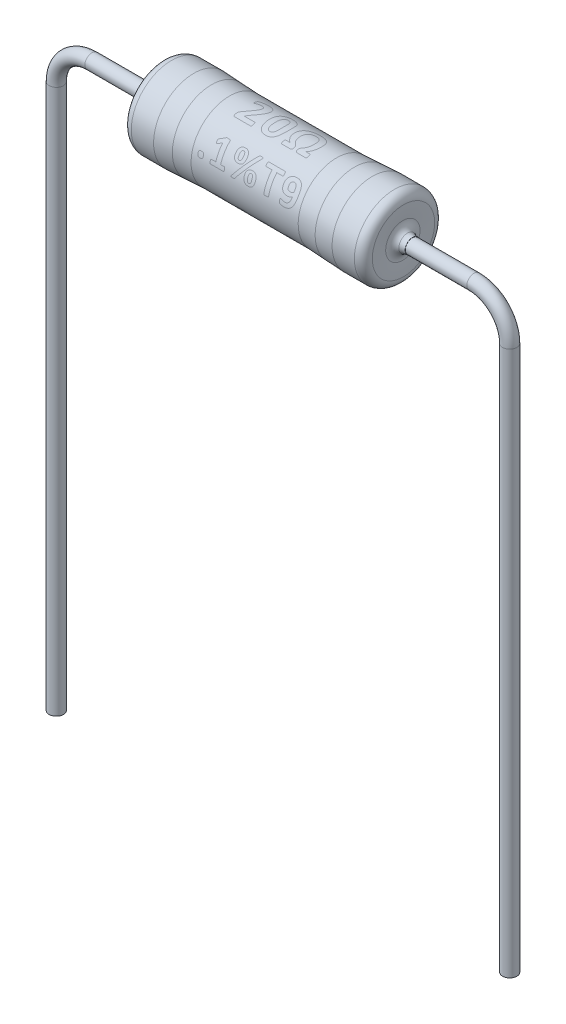
SolidWorks part; units mm, degrees
other "WIRE"
other "RESISTOR"
ref_plane "Front Plane" through (0, 0, 0) normal (0, 0, 1) x (1, 0, 0)
ref_plane "Top Plane" through (0, 0, 0) normal (0, 1, 0) x (1, 0, 0)
ref_plane "Right Plane" through (0, 0, 0) normal (1, 0, 0) x (0, 0, -1)
sketch "Sketch Wire Length" plane through (0, 0, 0) normal (0, 0, 1) x (1, 0, 0)
  line L0 (-10.7, 0) -> (10.7, 0)
  line L1 (12.7, -2) -> (12.7, -32.5084)
  line L2 (-12.7, -2) -> (-12.7, -32.5084)
  arc A0 (-10.7, 0) -> (-12.7, -2) centre (-10.7, -2) ccw
  arc A1 (10.7, 0) -> (12.7, -2) centre (10.7, -2) cw
  dimension "D2" = 2
  dimension "D3" = 88.7
  dimension "D1" = 25.4
sketch "Sketch Wire Diameter" plane through (0, 0, 0) normal (1, 0, 0) x (0, 0, -1)
  circle A0 centre (0, 0) radius 0.4
  dimension "D1" = 0.8
sweep "SET WIRE LENGTH" add profiles "Sketch Wire Diameter" path "Sketch Wire Length"
sketch "Sketch4" plane through (0, 0, 0) normal (0, 0, 1) x (1, 0, 0)
  line L0 (-7.25, 0) -> (7.25, 0)
  line L1 (7.25, 0) -> (7.25, 0.41)
  line L2 (-7.25, 0) -> (-7.25, 0.41)
  line L3 (0, 0) -> (0, 2.15) construction
  line L4 (0, 2.15) -> (0, 2.2) construction
  line L5 (-3, 2.15) -> (3, 2.15)
  line L6 (-4, 2.2) -> (4, 2.2) construction
  line L7 (0, 2.2) -> (0, 2.25) construction
  line L8 (-5, 2.25) -> (5, 2.25) construction
  line L9 (-5, 2.25) -> (-6.75, 2.25)
  line L10 (5, 2.25) -> (6.75, 2.25)
  line L11 (-6.75, 2.25) -> (-6.75, 1.81)
  line L12 (6.75, 2.25) -> (6.75, 1.81)
  line L13 (-6.75, 1.81) -> (-6.75, 0.81) construction
  line L14 (-6.75, 0.81) -> (-6.7, 0.81) construction
  line L15 (6.75, 1.81) -> (6.75, 0.81) construction
  line L16 (6.75, 0.81) -> (6.7, 0.81) construction
  line L17 (-7.25, 0.41) -> (7.25, 0.41) construction
  arc A0 (-3, 2.15) -> (-4, 2.2) centre (-3, 12.175) cw
  arc A1 (3, 2.15) -> (4, 2.2) centre (3, 12.175) ccw
  arc A2 (-5, 2.25) -> (-4, 2.2) centre (-5, -7.775) cw
  arc A3 (4, 2.2) -> (5, 2.25) centre (5, -7.775) cw
  arc A4 (-6.75, 1.81) -> (-6.7, 0.81) centre (3.275, 1.81) ccw
  arc A5 (-7.25, 0.41) -> (-6.7, 0.81) centre (-7.25, 0.9881) ccw
  arc A6 (6.75, 1.81) -> (6.7, 0.81) centre (-3.275, 1.81) cw
  arc A7 (6.7, 0.81) -> (7.25, 0.41) centre (7.25, 0.9881) ccw
  dimension "D7" = 13.5
  dimension "D8" = 1
  dimension "D10" = 0.4
  dimension "D1" = 14.5
  dimension "D2" = 0.41
  dimension "D3" = 2.15
  dimension "D4" = 2.25
  dimension "D5" = 6
  dimension "D6" = 8
  dimension "D9" = 0.05
revolve "Revolve1" add sketch "Sketch4" angle 360 about L0
fillet "Fillet1" radius 0.5 2 edges at (6.7, -0.81, 0) (-6.7, -0.81, 0)
fillet "Fillet2" radius 0.5 2 edges at (6.75, -2.25, 0) (-6.75, -2.25, 0)
ref_plane "Plane1" through (0, 10, 0) normal (0, 1, 0) x (1, 0, 0)
sketch "SketchSpecs" plane through (0, 10, 0) normal (0, 1, 0) x (1, 0, 0)
  line L0 (0, 0.75) -> (0, -0.75) construction
  line L1 (-3, -0.75) -> (3, -0.75) construction
  line L2 (-3, -2.15) -> (-3, 2.15) construction
  line L3 (0, 0.75) -> (0, 1.55) construction
  line L4 (-3, 1.55) -> (3, 1.55) construction
  line L5 (0, -0.75) -> (0, -2.95) construction
  line L6 (-3, -2.95) -> (3, -2.95) construction
  text T0 "20Ω" font "Calibri" height 1.5
  text T1 "CPF 3" font "Calibri" height 1.3
  text T2 ".1%T9" font "Calibri" height 1.3
  dimension "D1" = 1.5
  dimension "D2" = 0.8
  dimension "D3" = 2.2
wrap "Wrap SPECS" sketch "SketchSpecs" wrap type scribe source sketch "SketchSpecs" face at (-3, -2.15, 0)
ref_plane "Plane2" through (0, -4, 0) normal (0, 1, 0) x (1, 0, 0)
sketch "Sketch5" plane through (0, -4, 0) normal (0, 1, 0) x (1, 0, 0)
  line L0 (0, -0.6) -> (0, 0) construction
  line L1 (0, 0) -> (0, 2) construction
  line L2 (-3, -0.6) -> (3, -0.6) construction
  line L3 (-3, 2) -> (3, 2) construction
  line L4 (-3, -2.15) -> (-3, 2.15) construction
  text T0 "DALE" font "Calibri" height 1.4
  text T1 "2014" font "Calibri" height 1.4
  dimension "D1" = 0.6
  dimension "D2" = 2
wrap "Wrap1" sketch "Sketch5" wrap type scribe source sketch "Sketch5" face at (-3, -2.15, 0)
